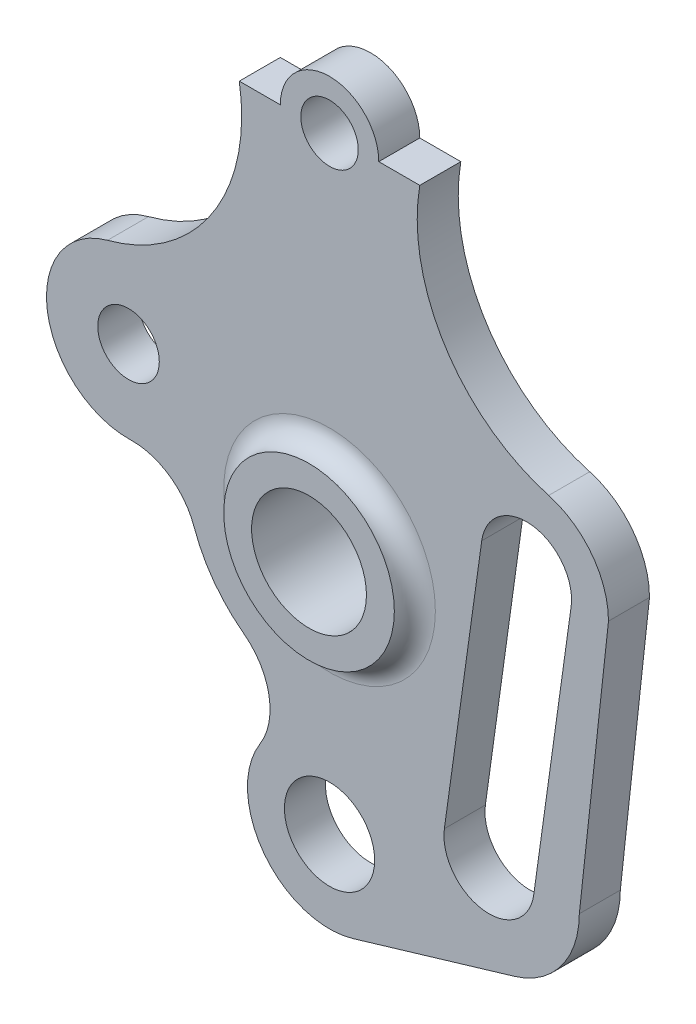
SolidWorks part; units mm, degrees
ref_plane "Front Plane" through (0, 0, 0) normal (0, 0, 1) x (1, 0, 0)
ref_plane "Top Plane" through (0, 0, 0) normal (0, 1, 0) x (1, 0, 0)
ref_plane "Right Plane" through (0, 0, 0) normal (1, 0, 0) x (0, 0, -1)
sketch "Sketch1" plane through (0, 0, 0) normal (0, 0, 1) x (1, 0, 0)
  line L0 (0, 0) -> (54101.9031, 0) construction
  line L1 (0, 0) -> (0, 54101.9031) construction
  line L2 (0, 0) -> (38.8887, -46.3457) construction
  line L3 (68, 19) -> (60.8887, -46.3457)
  line L4 (12, 88) -> (22, 88)
  line L5 (-22, 88) -> (-12, 88)
  line L6 (5.7022, -79.1699) -> (45.1611, -67.4326)
  line L7 (48, 19) -> (38.8887, -46.3457) construction
  line L8 (58.8946, 17.4809) -> (49.7833, -47.8648)
  line L9 (37.1054, 20.5191) -> (27.994, -44.8266)
  circle A0 centre (0, 0) radius 14
  arc A1 (-33.0011, -11.6587) -> (-20.9312, -28.0515) centre (0, 0) ccw
  circle A2 centre (0, 88) radius 7
  arc A3 (12, 88) -> (-12, 88) centre (0, 88) ccw
  arc A7 (19.7454, -57.1871) -> (19.8191, -57.3162) centre (38.8887, -46.3457) ccw
  arc A8 (-16.9443, -49.375) -> (5.7022, -79.1699) centre (0, -60) ccw
  circle A9 centre (0, -60) radius 11
  circle A10 centre (-49, 19) radius 7.5
  arc A11 (-54.1302, 38.3308) -> (-48.493, -0.9936) centre (-49, 19) ccw
  circle A12 centre (0, 0) radius 60.5 construction
  arc A13 (22, 88) -> (53.429, 38.2491) centre (65.3727, 80.597) ccw
  arc A14 (-22, 88) -> (-54.1302, 38.3308) centre (-65.4166, 80.8587) cw
  arc A15 (-48.493, -0.9936) -> (-33.0011, -11.6587) centre (-48.0874, -16.9884) cw
  arc A16 (-20.9312, -28.0515) -> (-16.9443, -49.375) centre (-30.4997, -40.875) cw
  arc A17 (58.8946, 17.4809) -> (37.1054, 20.5191) centre (48, 19) ccw
  arc A18 (67.5318, 14.6979) -> (53.429, 38.2491) centre (48, 19) ccw
  arc A19 (45.1611, -67.4326) -> (60.8887, -46.3457) centre (38.8887, -46.3457) ccw
  arc A20 (19.8191, -57.3162) -> (19.7986, -57.1688) centre (0, -60) ccw
  arc A21 (27.994, -44.8266) -> (49.7833, -47.8648) centre (38.8887, -46.3457) ccw
  circle A22 centre (0, 0) radius 20.7992
  point P3 (43.4443, -13.6728)
  point P29 (0, 88)
  dimension "D1" = 28
  dimension "D2" = 70
  dimension "D3" = 24
  dimension "D4" = 14
  dimension "D5" = 20
  dimension "D6" = 44
  dimension "D7" = 40
  dimension "D8" = 22
  dimension "D9" = 40
  dimension "D10" = 15
  dimension "D16" = 121
  dimension "D20" = 44
  dimension "D21" = 16
  dimension "D22" = 65.7315
  dimension "D23" = 11
  dimension "D24" = 41.5984
  dimension "D11" = 40
  dimension "D12" = 48
  dimension "D13" = 19
  dimension "D14" = 88
  dimension "D15" = 60
  dimension "D17" = 49
  dimension "D18" = 69
  dimension "D19" = 22
extrude "Boss-Extrude2" add sketch "Sketch1" along normal mid plane 20 contours A22 A0 region at (-20.2109, 0, 0)
extrude "Boss-Extrude3" add sketch "Sketch1<5>" along normal mid plane 10 contours L6 A19 L3 A18 A13 L4 A3 L5 A14 A11 A15 A1 A16 A8 A22 A21 L9 A17 L8 A2 A9 A10 region at (65.5171, 17.0937, 0)
sketch "Sketch1<5>" plane through (0, 0, 0) normal (0, 0, 1) x (1, 0, 0) same geometry as "Sketch1"
fillet "Fillet1" radius 5 1 edges at (20.7992, 0, 5)
